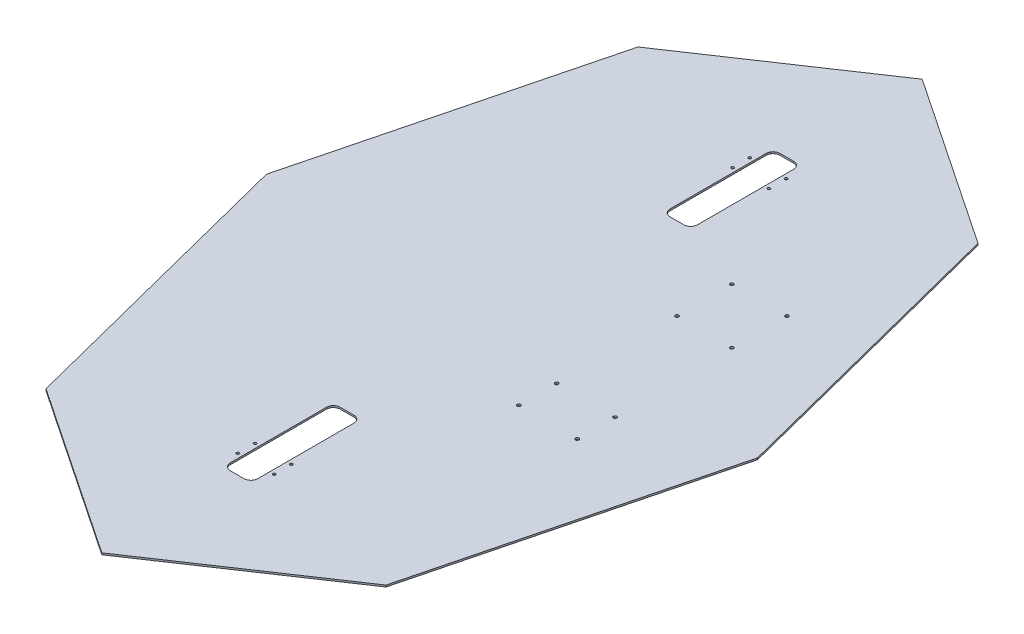
SolidWorks part; units mm, degrees
material "AISI 1020"
ref_plane "Front Plane" through (0, 0, 0) normal (0, 0, 1) x (1, 0, 0)
ref_plane "Top Plane" through (0, 0, 0) normal (0, 1, 0) x (1, 0, 0)
ref_plane "Right Plane" through (0, 0, 0) normal (1, 0, 0) x (0, 0, -1)
sketch "Sketch1" plane through (0, 0, 0) normal (0, 1, 0) x (1, 0, 0)
  line L0 (0, -549.0794) -> (0, 549.0794) construction
  line L1 (-314.2347, 547.1196) -> (-453.9232, 0)
  line L2 (-314.2347, -547.1196) -> (-453.9232, 0)
  line L3 (0, -758.1753) -> (-314.2347, -547.1196)
  line L4 (314.2347, -547.1196) -> (0, -758.1753)
  line L5 (317.0112, 0) -> (-317.0112, 0) construction
  line L6 (314.2347, -547.1196) -> (453.9232, 0)
  line L7 (453.9232, 0) -> (314.2347, 547.1196)
  line L8 (314.2347, 547.1196) -> (0, 758.1753)
  line L9 (-314.2347, 547.1196) -> (0, 758.1753)
  line L23 (-317.0112, -549.0794) -> (-457.2, 0) construction
  line L24 (0, -762) -> (-317.0112, -549.0794) construction
  line L25 (317.0112, -549.0794) -> (0, -762) construction
  line L26 (317.0112, -549.0794) -> (457.2, 0) construction
  line L27 (457.2, 0) -> (317.0112, 549.0794) construction
  line L28 (317.0112, 549.0794) -> (0, 762) construction
  line L29 (-317.0112, 549.0794) -> (0, 762) construction
  line L30 (-317.0112, 549.0794) -> (-457.2, 0) construction
  line L39 (-317.0112, -549.0794) -> (317.0112, -549.0794) construction
  line L40 (-317.0112, -549.0794) -> (-317.0112, 549.0794) construction
  line L41 (-317.0112, 549.0794) -> (317.0112, 549.0794) construction
  line L42 (317.0112, -549.0794) -> (317.0112, 549.0794) construction
  line L43 (-317.0112, -549.0794) -> (317.0112, 549.0794) construction
  line L44 (-317.0112, 549.0794) -> (317.0112, -549.0794) construction
  ellipse E0 centre (0, 0) end of major axis (0, 762) minor radius 457.2 construction
  point P50 (0, 0)
  dimension "D1" = 3.175
  dimension "D3" = 30
  dimension "D8" = 762
  dimension "D9" = 457.2
extrude "Boss-Extrude1" add sketch "Sketch1" along normal mid plane 3.175
sketch "Sketch2" plane through (0, 0, 0) normal (0, 1, 0) x (1, 0, 0)
  line L1 (82.55, -457.2) -> (-82.55, -457.2) construction
  line L2 (82.55, -457.2) -> (82.55, 457.2) construction
  line L3 (82.55, 457.2) -> (-82.55, 457.2) construction
  line L4 (-82.55, -457.2) -> (-82.55, 457.2) construction
  line L5 (0, 457.2) -> (0, -457.2) construction
  line L6 (33.528, 441.325) -> (-33.528, 441.325) construction
  line L7 (-25.4, 304.8) -> (25.4, 304.8)
  line L8 (-25.4, 304.8) -> (-25.4, 508)
  line L9 (-25.4, 508) -> (25.4, 508)
  line L10 (25.4, 304.8) -> (25.4, 508)
  line L11 (33.528, 441.325) -> (33.528, 473.075) construction
  line L17 (-82.55, 0) -> (82.55, 0) construction
  line L18 (33.528, 473.075) -> (-33.528, 473.075) construction
  line L19 (-33.528, 441.325) -> (-33.528, 473.075) construction
  line L22 (33.528, 441.325) -> (-33.528, 473.075) construction
  line L23 (33.528, 473.075) -> (-33.528, 441.325) construction
  circle A0 centre (-33.528, 473.075) radius 2.54
  circle A1 centre (-33.528, 441.325) radius 2.54
  circle A2 centre (33.528, 441.325) radius 2.54
  circle A3 centre (33.528, 473.075) radius 2.54
  point P0 (0, 0)
  point P3 (13.7562, 508)
  point P10 (0, 0)
  point P11 (0, 508)
  point P36 (0, 0)
  dimension "D7" = 5.08
  dimension "D1" = 165.1
  dimension "D2" = 914.4
  dimension "D3" = 50.8
  dimension "D4" = 203.2
  dimension "D6" = 31.75
  dimension "D8" = 50.8
  dimension "D10" = 67.056
extrude "Cut-Extrude1" cut sketch "Sketch2" against normal through all both and the other way through all contours L10 L9 L8 L7 | A3 | A2 | A1 | A0
fillet "Fillet1" radius 12.7 4 edges at (-25.4, 0, -508) (25.4, 0, -508) (25.4, 0, -304.8) (-25.4, 0, -304.8)
sketch "Sketch4" plane through (0, 1.5875, 0) normal (0, 1, 0) x (1, 0, 0)
  line L1 (149.225, -66.675) -> (257.175, -66.675) construction
  line L2 (149.225, -66.675) -> (149.225, -136.525) construction
  line L3 (149.225, -136.525) -> (257.175, -136.525) construction
  line L4 (257.175, -66.675) -> (257.175, -136.525) construction
  line L5 (149.225, -66.675) -> (257.175, -136.525) construction
  line L6 (149.225, -136.525) -> (257.175, -66.675) construction
  line L7 (152.4, 254) -> (254, 254) construction
  line L8 (152.4, 254) -> (152.4, 152.4) construction
  line L9 (152.4, 152.4) -> (254, 152.4) construction
  line L10 (254, 254) -> (254, 152.4) construction
  line L11 (152.4, 254) -> (254, 152.4) construction
  line L12 (152.4, 152.4) -> (254, 254) construction
  circle A0 centre (257.175, -66.675) radius 3.175
  circle A1 centre (149.225, -66.675) radius 3.175
  circle A2 centre (149.225, -136.525) radius 3.175
  circle A3 centre (257.175, -136.525) radius 3.175
  circle A4 centre (152.4, 254) radius 3.175
  circle A5 centre (254, 254) radius 3.175
  circle A6 centre (254, 152.4) radius 3.175
  circle A7 centre (152.4, 152.4) radius 3.175
  point P0 (203.2, -101.6)
  point P9 (203.2, 203.2)
  dimension "D1" = 6.35
  dimension "D8" = 6.35
  dimension "D2" = 107.95
  dimension "D3" = 69.85
  dimension "D4" = 101.6
  dimension "D5" = 203.2
  dimension "D6" = 101.6
  dimension "D7" = 304.8
extrude "Cut-Extrude3" cut sketch "Sketch4" against normal up to next
mirror "Mirror1" about plane through (0, 0, 0) normal (0, 0, 1) of "Fillet1", "Cut-Extrude1"
